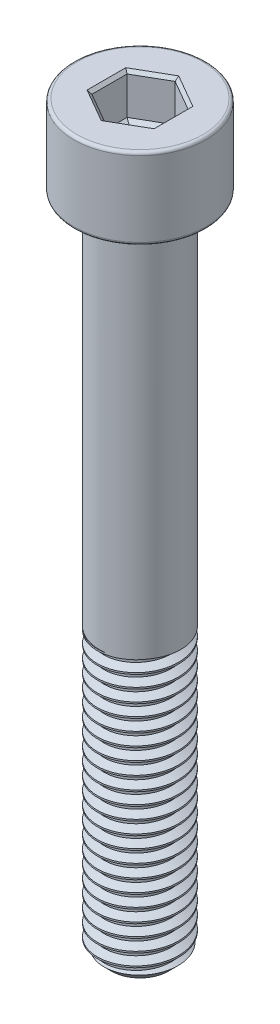
SolidWorks part; units mm, degrees
material "AISI Type A2 Tool Steel"
ref_plane "Front Plane" through (0, 0, 0) normal (0, 0, 1) x (1, 0, 0)
ref_plane "Top Plane" through (0, 0, 0) normal (0, 1, 0) x (1, 0, 0)
ref_plane "Right Plane" through (0, 0, 0) normal (1, 0, 0) x (0, 0, -1)
sketch "Sketch1" plane through (0, 0, 0) normal (0, 1, 0) x (1, 0, 0)
  circle A0 centre (0, 0) radius 4
  dimension "D1" = 8
extrude "Boss-Extrude1" add sketch "Sketch1" along normal blind 28
thread "Thread1" pitch 1.25 method cut profile "Thread Profile1" start angle 0, offset 2, length 0, pitch 1.25, diameter 8
ref_plane "Plane1" through (-4, 30, 0) normal (0, 0, 1) x (-1, 0, 0)
sketch "Thread Profile1" plane through (-4, 30, 0) normal (0, 0, 1) x (-1, 0, 0)
  line L0 (0, 0) -> (0, 1.25) construction
  line L11 (0, 0) -> (0, 1.0937)
  line L12 (0, 1.0937) -> (-0.6766, 0.7031)
  line L13 (-0.6766, 0.7031) -> (-0.6766, 0.3906)
  line L15 (-0.6766, 0.3906) -> (0, 0)
  line L17 (-0.6766, 0.5469) -> (0, 0.5469) construction
  point P2 (0, 0)
  dimension "Pitch" = 1.25
  dimension "Profile_Angle" = 60
  dimension "Profile_Land" = 0.3125
  dimension "Profile_Height" = 0.6766
sketch "Sketch2" plane through (0, 28, 0) normal (0, 1, 0) x (1, 0, 0)
  circle A0 centre (0, 0) radius 4
  dimension "D1" = 8
extrude "Boss-Extrude2" add sketch "Sketch2" along normal blind 37
sketch "Sketch5" plane through (0, 65, 0) normal (0, 1, 0) x (1, 0, 0)
  circle A0 centre (0, 0) radius 6.5
  dimension "D1" = 13
extrude "Boss-Extrude3" add sketch "Sketch5" along normal blind 8
sketch "Sketch6" plane through (0, 0, 0) normal (0, 0, 1) x (1, 0, 0)
  line L0 (0, 0) -> (0, 0.7245) construction
  line L1 (0, 0) -> (4.01, 0) construction
  line L2 (4.01, 0) -> (4.01, 1.2)
  line L3 (4.01, 1.2) -> (2.81, 0)
  line L4 (2.81, 0) -> (4.01, 0)
  dimension "D1" = 1.2
  dimension "D2" = 45
  dimension "D3" = 4.01
revolve "Cut-Revolve1" cut sketch "Sketch6" angle 360 about L0
fillet "Fillet1" radius 0.3 2 edges at (0, 65, 6.5) (0, 73, 6.5)
sketch "Sketch7" plane through (0, 73, 0) normal (0, 1, 0) x (1, 0, 0)
  line L1 (0, 3.4641) -> (-3, 1.7321)
  line L2 (-3, 1.7321) -> (-3, -1.7321)
  line L3 (-3, -1.7321) -> (0, -3.4641)
  line L4 (0, -3.4641) -> (3, -1.7321)
  line L5 (3, -1.7321) -> (3, 1.7321)
  line L6 (3, 1.7321) -> (0, 3.4641)
  circle A0 centre (0, 0) radius 3 construction
  dimension "D1" = 6
extrude "Cut-Extrude1" cut sketch "Sketch7" against normal blind 4
chamfer "Chamfer1" distance 0.3 angle 45 6 edges at (-3, 73, 0) (-1.5, 73, 2.5981) (1.5, 73, 2.5981) (3, 73, 0) (1.5, 73, -2.5981) (-1.5, 73, -2.5981)
sketch "Sketch8" plane through (0, 69, 0) normal (0, 1, 0) x (1, 0, 0)
  line L1 (0, 3.4641) -> (-3, 1.7321)
  line L2 (-3, 1.7321) -> (-3, -1.7321)
  line L3 (-3, -1.7321) -> (0, -3.4641)
  line L4 (0, -3.4641) -> (3, -1.7321)
  line L5 (3, -1.7321) -> (3, 1.7321)
  line L6 (3, 1.7321) -> (0, 3.4641)
  circle A0 centre (0, 0) radius 3 construction
extrude "Cut-Extrude2" cut sketch "Sketch8" against normal blind 0.4 draft 60
